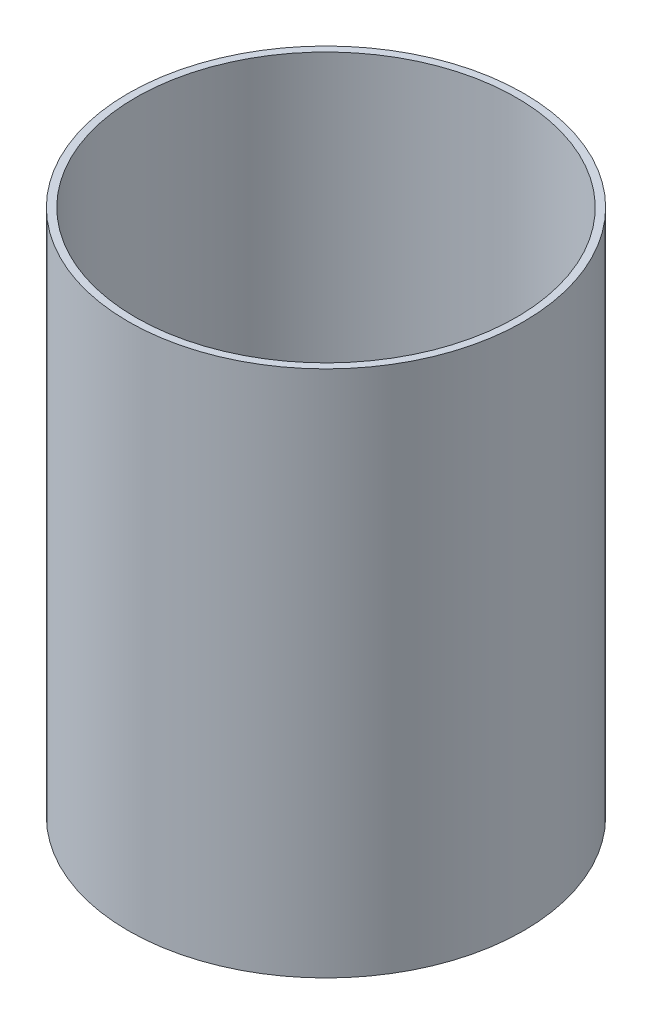
SolidWorks part; units mm, degrees
material "E-Glass Fiber"
ref_plane "Front Plane" through (0, 0, 0) normal (0, 0, 1) x (1, 0, 0)
ref_plane "Top Plane" through (0, 0, 0) normal (0, 1, 0) x (1, 0, 0)
ref_plane "Right Plane" through (0, 0, 0) normal (1, 0, 0) x (0, 0, -1)
sketch "Sketch1" plane through (0, 0, 0) normal (0, 1, 0) x (1, 0, 0)
  circle A0 centre (0, 0) radius 73.3425
  circle A1 centre (0, 0) radius 76.1746
  dimension "D1" = 146.685
  dimension "D2" = 152.3492
extrude "Boss-Extrude1" add sketch "Sketch1" along normal blind 203.2
equation "\"Length\"= 8"
equation "\"Outer Diameter\"= 5.998"
equation "\"Inner Diameter\"= 5.775"
equation "\"Wall Thickness\"= 0.111"
equation "\"D1@Sketch1\"=\"Inner Diameter\""
equation "\"D2@Sketch1\"=\"Outer Diameter\""
equation "\"D1@Boss-Extrude1\"=\"Length\""
